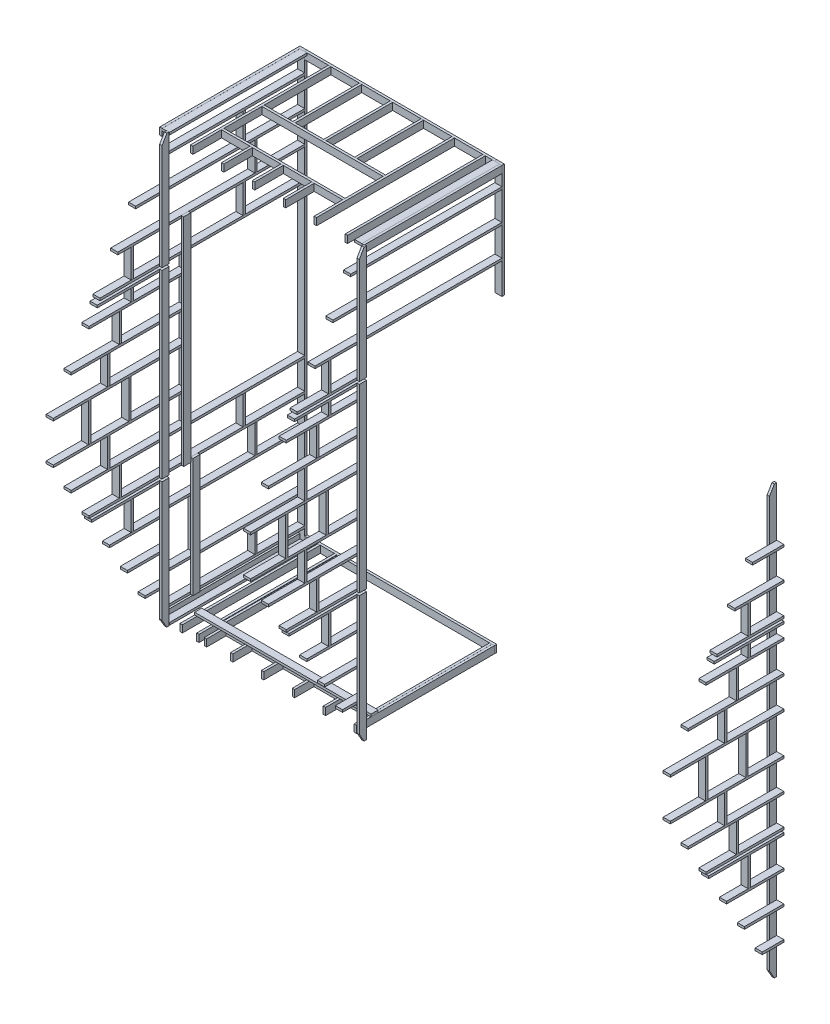
SolidWorks part; units mm, degrees
ref_plane "Спереди" through (0, 0, 0) normal (0, 0, 1) x (1, 0, 0)
ref_plane "Сверху" through (0, 0, 0) normal (0, 1, 0) x (1, 0, 0)
ref_plane "Справа" through (0, 0, 0) normal (1, 0, 0) x (0, 0, -1)
other "Configuration Table"
sketch "Эскиз2" plane through (-110, 0, 0) normal (-1, 0, 0) x (0, 0, 1)
  line L0 (-50, 0) -> (-50, 6600) construction
  line L1 (-50, 2700) -> (1529.9782, 2700)
  line L2 (-50, 2700) -> (-50, 2650)
  line L3 (-50, 2650) -> (1529.9782, 2650)
  line L4 (1529.9782, 2700) -> (1529.9782, 2650)
  line L5 (-50, 4100) -> (2338.2686, 4100)
  line L6 (-50, 4100) -> (-50, 4050)
  line L7 (-50, 4050) -> (2338.2686, 4050)
  line L8 (2338.2686, 4100) -> (2338.2686, 4050)
  line L9 (2651.9993, 4500) -> (-50, 4500) construction
  line L10 (-50, 8900) -> (-50, 100) construction
  line L11 (0, 0) -> (2598.0762, 4500) construction
  line L12 (2651.9993, 4500) -> (53.923, 0) construction
  line L13 (0, 9000) -> (2598.0762, 4500) construction
  line L14 (1550, 4100) -> (750, 4100) construction
  line L15 (-50, 4900) -> (-50, 4950)
  line L16 (-50, 4900) -> (2338.2686, 4900)
  line L17 (2338.2686, 4900) -> (2338.2686, 4950)
  line L18 (-50, 4950) -> (2338.2686, 4950)
  line L19 (1550, 4100) -> (1550, 4900) construction
  line L28 (1550, 4899) -> (1600, 4899)
  line L29 (1550, 4899) -> (1550, 4101)
  line L30 (1550, 4101) -> (1600, 4101)
  line L31 (1600, 4899) -> (1600, 4101)
  line L32 (750, 4100) -> (750, 4900) construction
  line L33 (750, 4899) -> (700, 4899)
  line L34 (750, 4899) -> (750, 4101)
  line L35 (750, 4101) -> (700, 4101)
  line L36 (700, 4899) -> (700, 4101)
  line L38 (1962.9909, 3400) -> (-50, 3400)
  line L39 (1962.9909, 3400) -> (1962.9909, 3450)
  line L40 (1962.9909, 3450) -> (-50, 3450)
  line L41 (-50, 3400) -> (-50, 3450)
  line L43 (-50, 2800) -> (1587.7132, 2800)
  line L44 (-50, 2800) -> (-50, 2750)
  line L45 (-50, 2750) -> (1587.7132, 2750)
  line L46 (1587.7132, 2800) -> (1587.7132, 2750)
  line L47 (1154.7005, 2000) -> (-50, 2000)
  line L48 (1154.7005, 2000) -> (1154.7005, 2050)
  line L49 (1154.7005, 2050) -> (-50, 2050)
  line L50 (-50, 2000) -> (-50, 2050)
  line L51 (779.4229, 1350) -> (-50, 1350)
  line L52 (779.4229, 1350) -> (779.4229, 1400)
  line L53 (779.4229, 1400) -> (-50, 1400)
  line L54 (-50, 1350) -> (-50, 1400)
  line L55 (404.1452, 700) -> (-50, 700)
  line L56 (404.1452, 700) -> (404.1452, 750)
  line L57 (404.1452, 750) -> (-50, 750)
  line L58 (-50, 700) -> (-50, 750)
  line L59 (1200, 4049) -> (1150, 4049)
  line L60 (1200, 4049) -> (1200, 3451)
  line L61 (1200, 3451) -> (1150, 3451)
  line L62 (1150, 4049) -> (1150, 3451)
  line L63 (950, 3399) -> (900, 3399)
  line L64 (950, 3399) -> (950, 2801)
  line L65 (950, 2801) -> (900, 2801)
  line L66 (900, 3399) -> (900, 2801)
  line L67 (700, 2649) -> (650, 2649)
  line L68 (700, 2649) -> (700, 2051)
  line L69 (700, 2051) -> (650, 2051)
  line L70 (650, 2649) -> (650, 2051)
  line L71 (1200, 4951) -> (1150, 4951)
  line L80 (900, 5601) -> (900, 6199)
  line L81 (950, 6199) -> (900, 6199)
  line L82 (950, 5601) -> (950, 6199)
  line L83 (950, 5601) -> (900, 5601)
  line L84 (1150, 4951) -> (1150, 5549)
  line L85 (1200, 5549) -> (1150, 5549)
  line L86 (1200, 4951) -> (1200, 5549)
  line L95 (1587.7132, 6200) -> (1587.7132, 6250)
  line L96 (-50, 6250) -> (1587.7132, 6250)
  line L97 (-50, 6200) -> (-50, 6250)
  line L98 (-50, 6200) -> (1587.7132, 6200)
  line L99 (-50, 5600) -> (-50, 5550)
  line L100 (1962.9909, 5550) -> (-50, 5550)
  line L101 (1962.9909, 5600) -> (1962.9909, 5550)
  line L102 (1962.9909, 5600) -> (-50, 5600)
  line L107 (-50, 4500) -> (-50, 9000) construction
  line L108 (-50, 9000) -> (0, 9000) construction
  line L110 (-50, 6550) -> (1414.5082, 6550)
  line L111 (-50, 6550) -> (-50, 6500)
  line L112 (-50, 6500) -> (1414.5082, 6500)
  line L113 (1414.5082, 6550) -> (1414.5082, 6500)
  line L114 (-50, 6600) -> (1356.7731, 6600)
  line L115 (-50, 6600) -> (-50, 6650)
  line L116 (-50, 6650) -> (1356.7731, 6650)
  line L117 (1356.7731, 6600) -> (1356.7731, 6650)
  line L118 (-50, 7300) -> (981.4955, 7300)
  line L119 (-50, 7300) -> (-50, 7250)
  line L120 (-50, 7250) -> (981.4955, 7250)
  line L121 (981.4955, 7300) -> (981.4955, 7250)
  line L122 (650, 6499) -> (700, 6499)
  line L123 (650, 6499) -> (650, 6251)
  line L124 (650, 6251) -> (700, 6251)
  line L125 (700, 6499) -> (700, 6251)
  line L126 (650, 7249) -> (700, 7249)
  line L127 (650, 7249) -> (650, 6651)
  line L128 (650, 6651) -> (700, 6651)
  line L129 (700, 7249) -> (700, 6651)
  line L130 (-50, 7950) -> (606.2178, 7950)
  line L131 (-50, 7950) -> (-50, 7900)
  line L132 (-50, 7900) -> (606.2178, 7900)
  line L133 (606.2178, 7950) -> (606.2178, 7900)
  dimension "D1" = 50
  dimension "D2" = 800
  dimension "D3" = 1
  dimension "D4" = 1
  dimension "D5" = 600
  dimension "D6" = 600
  dimension "D7" = 600
  dimension "D8" = 600
  dimension "D9" = 600
  dimension "D10" = 1
  dimension "D11" = 1
  dimension "D12" = 400
  dimension "D13" = 1
  dimension "D14" = 1
  dimension "D15" = 200
  dimension "D16" = 200
  dimension "D17" = 1
  dimension "D18" = 1
  dimension "D19" = 200
  dimension "D20" = 600
  dimension "D21" = 1
  dimension "D22" = 1
  dimension "D23" = 600
ref_plane "Плоскость1" through (-8990, 0, 0) normal (1, 0, 0) x (0, 0, -1)
ref_plane "Плоскость2" through (-13140, 0, 0) normal (1, 0, 0) x (0, 0, -1)
extrude "Бобышка-Вытянуть1" add sketch "Эскиз2" along normal blind 50 and the other way blind 100
extrude "Бобышка-Вытянуть2" add sketch "Эскиз2<2>" against normal blind 150 from surface separate body starting at plane "Плоскость1"
sketch "Эскиз2<2>" plane through (-110, 0, 0) normal (-1, 0, 0) x (0, 0, 1) same geometry as "Эскиз2"
extrude "Бобышка-Вытянуть3" add sketch "Эскиз2<3>" against normal blind 150 from surface separate body starting at plane "Плоскость2"
sketch "Эскиз2<3>" plane through (-110, 0, 0) normal (-1, 0, 0) x (0, 0, 1) same geometry as "Эскиз2"
sketch "Эскиз3" plane through (-160, 0, 0) normal (-1, 0, 0) x (0, 0, 1)
  line L0 (0, 0) -> (100, 173.2051)
  line L1 (-50, 2700) -> (100, 2700)
  line L2 (-50, 2700) -> (-50, 0)
  line L3 (-50, 0) -> (0, 0)
  line L4 (100, 2700) -> (100, 173.2051)
  line L5 (0, 0) -> (2598.0762, 4500) construction
  line L7 (-50, 2750) -> (100, 2750)
  line L8 (-50, 2750) -> (-50, 6550)
  line L9 (-50, 6550) -> (100, 6550)
  line L10 (100, 2750) -> (100, 6550)
  line L11 (-50, 6600) -> (1356.7731, 6600) construction
  line L12 (2598.0762, 4500) -> (-50, 4500) construction
  line L13 (-50, 6600) -> (100, 6600)
  line L14 (100, 6600) -> (100, 8826.7949)
  line L15 (0, 9000) -> (100, 8826.7949)
  line L16 (-50, 9000) -> (0, 9000)
  line L17 (-50, 6600) -> (-50, 9000)
  line L18 (1414.5082, 6550) -> (-50, 6550) construction
  dimension "D1" = 150
extrude "Бобышка-Вытянуть4" add sketch "Эскиз3" along normal blind 50 separate body
extrude "Бобышка-Вытянуть5" add sketch "Эскиз3<2>" against normal blind 50 from surface separate body starting at face at (-8840, 6950, 675)
sketch "Эскиз3<2>" plane through (-160, 0, 0) normal (-1, 0, 0) x (0, 0, 1) same geometry as "Эскиз3"
extrude "Бобышка-Вытянуть6" add sketch "Эскиз3<3>" against normal blind 50 from surface separate body starting at face at (-12990, 7275, 465.7477)
sketch "Эскиз3<3>" plane through (-160, 0, 0) normal (-1, 0, 0) x (0, 0, 1) same geometry as "Эскиз3"
ref_plane "Плоскость3" through (0, 0, -3000) normal (0, 0, -1) x (-1, 0, 0)
sketch "Эскиз4" plane through (0, 0, -3000) normal (0, 0, -1) x (-1, 0, 0)
  line L1 (8840, 8990) -> (8990, 8990)
  line L2 (8840, 8990) -> (8840, 6600)
  line L3 (8840, 6600) -> (8990, 6600)
  line L4 (8990, 8990) -> (8990, 6600)
  line L5 (12990, 8990) -> (13140, 8990)
  line L6 (12990, 8990) -> (12990, 10)
  line L7 (12990, 10) -> (13140, 10)
  line L8 (13140, 8990) -> (13140, 10)
  line L9 (8991, 8990) -> (12989, 8990)
  line L10 (8991, 8990) -> (8991, 8840)
  line L11 (8991, 8840) -> (12989, 8840)
  line L12 (12989, 8990) -> (12989, 8840)
  line L13 (9000, 160) -> (12989, 160)
  line L14 (9000, 160) -> (9000, 10)
  line L15 (9000, 10) -> (12989, 10)
  line L16 (12989, 160) -> (12989, 10)
  line L17 (8990, 7950) -> (8990, 7900) construction
  line L18 (12990, 6600) -> (12990, 9000) construction
  line L20 (12940, 0) -> (12990, 0) construction
  line L21 (8840, 6600) -> (8840, 9000) construction
  line L22 (8790, 9000) -> (8840, 9000) construction
  line L23 (8840, 6600) -> (8990, 6600) construction
  line L24 (8990, 6650) -> (8990, 6600) construction
  line L26 (9000, 203) -> (9000, 1000) construction
  point P26 (9000, 85)
  dimension "D1" = 1
  dimension "D2" = 150
  dimension "D3" = 1
  dimension "D4" = 1
  dimension "D5" = 10
  dimension "D6" = 10
extrude "Бобышка-Вытянуть7" add sketch "Эскиз4" against normal blind 50 separate body
sketch "Эскиз5" plane through (-8990, 0, 0) normal (-1, 0, 0) x (0, 0, 1)
  line L0 (-2950, 6600) -> (-2950, 8990) construction
  line L1 (-50, 7300) -> (-2950, 7300)
  line L2 (-50, 7300) -> (-50, 7250)
  line L3 (-50, 7250) -> (-2950, 7250)
  line L4 (-2950, 7300) -> (-2950, 7250)
  line L5 (-50, 7900) -> (606.2178, 7900) construction
  line L6 (-50, 7950) -> (-2950, 7950)
  line L7 (-50, 7950) -> (-50, 7900)
  line L8 (-50, 7900) -> (-2950, 7900)
  line L9 (-2950, 7950) -> (-2950, 7900)
  line L10 (230.9401, 8600) -> (-2950, 8600)
  line L11 (230.9401, 8600) -> (230.9401, 8550)
  line L12 (230.9401, 8550) -> (-2950, 8550)
  line L13 (-2950, 8600) -> (-2950, 8550)
  line L14 (0, 9000) -> (2598.0762, 4500) construction
  dimension "D1" = 600
extrude "Бобышка-Вытянуть8" add sketch "Эскиз5" against normal up to vertex (150 mm away) separate body up to point (-8840, 7950, -50)
sketch "Эскиз6" plane through (-8840, 0, 0) normal (-1, 0, 0) x (0, 0, 1)
  line L1 (-2950, 8990) -> (-50, 8990)
  line L2 (-2950, 8990) -> (-2950, 8840)
  line L3 (-2950, 8840) -> (-50, 8840)
  line L4 (-50, 8990) -> (-50, 8840)
  line L5 (-50, 6600) -> (-50, 9000) construction
  point P5 (0, 0)
  point P6 (-50, 8990)
  dimension "D1" = 150
extrude "Бобышка-Вытянуть9" add sketch "Эскиз6" along normal blind 50 separate body
sketch "Эскиз7" plane through (0, 0, -2950) normal (0, 0, 1) x (1, 0, 0)
  line L0 (-8991, 8840) -> (-12989, 8840) construction
  line L1 (-13140, 8990) -> (-13090, 8990)
  line L2 (-13140, 8990) -> (-13140, 8840)
  line L3 (-13140, 8840) -> (-13090, 8840)
  line L4 (-13090, 8990) -> (-13090, 8840)
  line L5 (-8890, 8990) -> (-8840, 8990) construction
  line L6 (-13140, 8990) -> (-12990, 8990) construction
  line L7 (-13089, 8990) -> (-12939, 8990)
  line L8 (-13089, 8990) -> (-13089, 8940)
  line L9 (-13089, 8940) -> (-12939, 8940)
  line L10 (-12939, 8990) -> (-12939, 8940)
  line L11 (-12989, 8990) -> (-8991, 8990) construction
  line L12 (-9040, 8990) -> (-8890, 8990)
  line L13 (-9040, 8990) -> (-9040, 8940)
  line L14 (-9040, 8940) -> (-8890, 8940)
  line L15 (-8890, 8990) -> (-8890, 8940)
  line L16 (-8890, 8840) -> (-8890, 8990) construction
  line L17 (-8890, 8840) -> (-8840, 8840) construction
  line L19 (-12490, 8990) -> (-12440, 8990)
  line L20 (-12490, 8990) -> (-12490, 8840)
  line L21 (-12490, 8840) -> (-12440, 8840)
  line L22 (-12440, 8990) -> (-12440, 8840)
  line L23 (-11840, 8990) -> (-11790, 8990)
  line L24 (-11840, 8990) -> (-11840, 8840)
  line L25 (-11840, 8840) -> (-11790, 8840)
  line L26 (-11790, 8990) -> (-11790, 8840)
  line L27 (-11190, 8990) -> (-11140, 8990)
  line L28 (-11190, 8990) -> (-11190, 8840)
  line L29 (-11190, 8840) -> (-11140, 8840)
  line L30 (-11140, 8990) -> (-11140, 8840)
  line L31 (-10540, 8990) -> (-10490, 8990)
  line L32 (-10540, 8990) -> (-10540, 8840)
  line L33 (-10540, 8840) -> (-10490, 8840)
  line L34 (-10490, 8990) -> (-10490, 8840)
  line L35 (-9890, 8990) -> (-9840, 8990)
  line L36 (-9890, 8990) -> (-9890, 8840)
  line L37 (-9890, 8840) -> (-9840, 8840)
  line L38 (-9840, 8990) -> (-9840, 8840)
  line L39 (-9240, 8990) -> (-9190, 8990)
  line L40 (-9240, 8990) -> (-9240, 8840)
  line L41 (-9240, 8840) -> (-9190, 8840)
  line L42 (-9190, 8990) -> (-9190, 8840)
  dimension "D1" = 1
  dimension "D2" = 600
  dimension "D3" = 600
  dimension "D4" = 600
  dimension "D5" = 600
  dimension "D6" = 600
  dimension "D7" = 600
  dimension "D8" = 300
extrude "Бобышка-Вытянуть10" add sketch "Эскиз7" along normal up to surface (2900 mm away) separate body up to face at (-8865, 8915, -50)
sketch "Эскиз8" plane through (0, 9000, 0) normal (0, 1, 0) x (1, 0, 0)
  line L2 (-9890, 650) -> (-12440, 650)
  line L3 (-9890, 650) -> (-9890, 1550)
  line L4 (-9890, 1550) -> (-12440, 1550)
  line L5 (-12440, 650) -> (-12440, 1550)
  line L7 (-9890, 700) -> (-12440, 700) construction
  line L8 (-12440, 1500) -> (-9890, 1500) construction
  line L9 (-12440, 50) -> (-12440, 2950) construction
  line L10 (-9890, 50) -> (-9890, 2950) construction
  dimension "D1" = 50
  dimension "D2" = 50
extrude "Вырез-Вытянуть1" cut sketch "Эскиз8" against normal blind 488
sketch "Эскиз9" plane through (0, 8840, 0) normal (0, -1, 0) x (1, 0, 0)
  line L0 (-12440, -50) -> (-12440, -2950) construction
  line L1 (-12440, -650) -> (-9890, -650)
  line L2 (-12440, -650) -> (-12440, -700)
  line L3 (-12440, -700) -> (-9890, -700)
  line L4 (-9890, -650) -> (-9890, -700)
  line L7 (-12440, -1500) -> (-9890, -1500)
  line L8 (-12440, -1500) -> (-12440, -1550)
  line L9 (-12440, -1550) -> (-9890, -1550)
  line L10 (-9890, -1500) -> (-9890, -1550)
  line L11 (-11840, -650) -> (-11790, -650) construction
  line L12 (-9890, -50) -> (-9890, -2950) construction
  line L13 (-11140, -1550) -> (-11190, -1550) construction
  line L14 (-9840, -50) -> (-9890, -50) construction
extrude "Бобышка-Вытянуть11" add sketch "Эскиз9" against normal up to surface (150 mm away) separate body up to face at (-8915, 8990, -2975)
combine bodies "Соединить1" operation type add bodies to combine 142 185
combine bodies "Соединить2" operation type add bodies to combine 179 186
sketch "Эскиз10" plane through (-12990, 0, 0) normal (1, 0, 0) x (0, 0, -1)
  line L0 (505.6624, 3450) -> (505.6624, 6600) construction
  line L1 (50, 6600) -> (2950, 6600)
  line L2 (50, 6600) -> (50, 6650)
  line L3 (50, 6650) -> (2950, 6650)
  line L4 (2950, 6600) -> (2950, 6650)
  line L5 (50, 7250) -> (2950, 7250)
  line L6 (50, 7250) -> (50, 7300)
  line L7 (50, 7300) -> (2950, 7300)
  line L8 (2950, 7250) -> (2950, 7300)
  line L9 (50, 7900) -> (2950, 7900)
  line L10 (50, 7900) -> (50, 7950)
  line L11 (50, 7950) -> (2950, 7950)
  line L12 (2950, 7900) -> (2950, 7950)
  line L13 (50, 6200) -> (454.6624, 6200)
  line L14 (50, 6200) -> (50, 6250)
  line L15 (50, 6250) -> (454.6624, 6250)
  line L17 (50, 5550) -> (454.6624, 5550)
  line L18 (50, 5550) -> (50, 5600)
  line L19 (50, 5600) -> (454.6624, 5600)
  line L20 (454.6624, 5550) -> (454.6624, 5600)
  line L21 (50, 4900) -> (454.6624, 4900)
  line L22 (50, 4900) -> (50, 4950)
  line L23 (50, 4950) -> (454.6624, 4950)
  line L24 (454.6624, 4900) -> (454.6624, 4950)
  line L25 (50, 4050) -> (454.6624, 4050)
  line L26 (50, 4050) -> (50, 4100)
  line L27 (50, 4100) -> (454.6624, 4100)
  line L28 (454.6624, 4050) -> (454.6624, 4100)
  line L29 (50, 3400) -> (2950, 3400)
  line L30 (50, 3400) -> (50, 3450)
  line L31 (50, 3450) -> (2950, 3450)
  line L32 (2950, 3400) -> (2950, 3450)
  line L33 (455.6624, 6599) -> (505.6624, 6599)
  line L34 (455.6624, 6599) -> (455.6624, 3451)
  line L35 (455.6624, 3451) -> (505.6624, 3451)
  line L36 (505.6624, 6599) -> (505.6624, 3451)
  line L37 (2950, 8990) -> (2950, 10) construction
  line L38 (50, 6600) -> (50, 9000) construction
  line L39 (-650, 6651) -> (-700, 6651) construction
  line L40 (-50, 6600) -> (-1166.3586, 6600) construction
  line L41 (50, 7250) -> (-981.4955, 7250) construction
  line L42 (50, 7900) -> (-606.2178, 7900) construction
  line L43 (50, 4050) -> (-2338.2686, 4050) construction
  line L44 (50, 4900) -> (-2338.2686, 4900) construction
  line L45 (50, 5550) -> (-1962.9909, 5550) construction
  line L46 (50, 6200) -> (-1587.7132, 6200) construction
  line L47 (-1962.9909, 3450) -> (50, 3450) construction
  line L48 (50, 0) -> (50, 2700) construction
  line L49 (50, 8550) -> (2950, 8550)
  line L50 (50, 8550) -> (50, 8600)
  line L51 (50, 8600) -> (2950, 8600)
  line L52 (2950, 8550) -> (2950, 8600)
  line L53 (50, 2750) -> (2950, 2750)
  line L54 (50, 2750) -> (50, 2800)
  line L55 (50, 2800) -> (2950, 2800)
  line L56 (2950, 2750) -> (2950, 2800)
  line L57 (50, 2100) -> (2950, 2100)
  line L58 (50, 2100) -> (50, 2150)
  line L59 (50, 2150) -> (2950, 2150)
  line L60 (2950, 2100) -> (2950, 2150)
  line L61 (-650, 2051) -> (-700, 2051) construction
  line L62 (700, 2100) -> (3000, 2100) construction
  line L63 (454.6624, 6250) -> (454.6624, 6200)
  line L68 (50, 2750) -> (50, 6550) construction
  line L73 (3000, 1000) -> (700, 1000) construction
  line L74 (50, 1000) -> (2950, 1000)
  line L75 (50, 1000) -> (50, 950)
  line L76 (50, 950) -> (2950, 950)
  line L77 (2950, 1000) -> (2950, 950)
  line L78 (700, 1000) -> (700, 2100) construction
  line L79 (700, 1001) -> (650, 1001)
  line L80 (700, 1001) -> (700, 2099)
  line L81 (700, 2099) -> (650, 2099)
  line L82 (650, 1001) -> (650, 2099)
  line L84 (50, 350) -> (2950, 350)
  line L85 (50, 350) -> (50, 300)
  line L86 (50, 300) -> (2950, 300)
  line L87 (2950, 350) -> (2950, 300)
  line L88 (1650, 3399) -> (1700, 3399)
  line L89 (1650, 3399) -> (1650, 2801)
  line L90 (1650, 2801) -> (1700, 2801)
  line L91 (1700, 3399) -> (1700, 2801)
  line L92 (1900, 2749) -> (1950, 2749)
  line L93 (1900, 2749) -> (1900, 2151)
  line L94 (1900, 2151) -> (1950, 2151)
  line L95 (1950, 2749) -> (1950, 2151)
  line L96 (1900, 949) -> (1950, 949)
  line L97 (1900, 949) -> (1900, 351)
  line L98 (1900, 351) -> (1950, 351)
  line L99 (1950, 949) -> (1950, 351)
  line L100 (1650, 8549) -> (1700, 8549)
  line L101 (1650, 8549) -> (1650, 7951)
  line L102 (1650, 7951) -> (1700, 7951)
  line L103 (1700, 8549) -> (1700, 7951)
  line L104 (1900, 7899) -> (1950, 7899)
  line L105 (1900, 7899) -> (1900, 7301)
  line L106 (1900, 7301) -> (1950, 7301)
  line L107 (1950, 7899) -> (1950, 7301)
  line L108 (1650, 7249) -> (1700, 7249)
  line L109 (1650, 7249) -> (1650, 6651)
  line L110 (1650, 6651) -> (1700, 6651)
  line L111 (1700, 7249) -> (1700, 6651)
  dimension "D1" = 1
  dimension "D2" = 1
  dimension "D3" = 1
  dimension "D4" = 600
  dimension "D5" = 1100
  dimension "D6" = 1
  dimension "D7" = 1
  dimension "D8" = 600
  dimension "D9" = 1000
  dimension "D10" = 200
  dimension "D11" = 1
  dimension "D12" = 1
  dimension "D13" = 1
  dimension "D14" = 1
  dimension "D15" = 1
  dimension "D16" = 1
  dimension "D17" = 1
extrude "Бобышка-Вытянуть12" add sketch "Эскиз10" against normal up to surface (150 mm away) separate body up to face at (-13140, 2025, 552.3503)
sketch "Эскиз11" plane through (-12990, 0, 0) normal (1, 0, 0) x (0, 0, -1)
  line L0 (50, 2750) -> (2950, 2750) construction
  line L1 (355.6624, 2750) -> (505.6624, 2750)
  line L2 (355.6624, 2750) -> (355.6624, 7300)
  line L3 (355.6624, 7300) -> (505.6624, 7300)
  line L4 (505.6624, 2750) -> (505.6624, 7300)
  line L5 (2950, 7300) -> (50, 7300) construction
  line L6 (-100, 2750) -> (50, 2750) construction
  line L7 (505.6624, 3451) -> (505.6624, 6599) construction
  line L8 (50, 300) -> (2950, 300) construction
  line L9 (550, 300) -> (700, 300)
  line L10 (550, 300) -> (550, 2800)
  line L11 (550, 2800) -> (700, 2800)
  line L12 (700, 300) -> (700, 2800)
  line L13 (2950, 2800) -> (50, 2800) construction
  line L14 (700, 1001) -> (700, 2099) construction
extrude "Бобышка-Вытянуть13" add sketch "Эскиз11" along normal blind 50 separate body
sketch "Эскиз12" plane through (0, 0, -2950) normal (0, 0, 1) x (1, 0, 0)
  line L1 (-9000, 10) -> (-12989, 10) construction
  line L2 (-13140, 10) -> (-13090, 10)
  line L3 (-13140, 10) -> (-13140, 160)
  line L4 (-13140, 160) -> (-13090, 160)
  line L5 (-13090, 10) -> (-13090, 160)
  line L6 (-12939, 10) -> (-13089, 10)
  line L7 (-12939, 10) -> (-12939, 60)
  line L8 (-12939, 60) -> (-13089, 60)
  line L9 (-13089, 10) -> (-13089, 60)
  line L10 (-12989, 10) -> (-12989, 160) construction
  line L12 (-12990, 300) -> (-12990, 350) construction
  dimension "D1" = 1
extrude "Бобышка-Вытянуть14" add sketch "Эскиз12" along normal up to surface (2900 mm away) separate body
sketch "Эскиз13" plane through (0, 10, 0) normal (0, 1, 0) x (1, 0, 0)
  line L0 (-12989, 2950) -> (-9000, 2950) construction
  line L1 (-9000, 2950) -> (-9050, 2950)
  line L2 (-9000, 2950) -> (-9000, 50)
  line L3 (-9000, 50) -> (-9050, 50)
  line L4 (-9050, 2950) -> (-9050, 50)
  line L8 (-9051, 2950) -> (-9100, 2950)
  line L9 (-9051, 2950) -> (-9051, 506.6624)
  line L10 (-9051, 506.6624) -> (-9100, 506.6624)
  line L11 (-9100, 2950) -> (-9100, 506.6624)
  line L12 (-9100, 505.6624) -> (-12250, 505.6624) construction
  line L17 (-9051, 505.6624) -> (-12300, 505.6624)
  line L18 (-9051, 505.6624) -> (-9051, 455.6624)
  line L19 (-9051, 455.6624) -> (-12300, 455.6624)
  line L20 (-12300, 505.6624) -> (-12300, 455.6624)
  line L24 (-12300, 2950) -> (-12250, 2950)
  line L25 (-12300, 2950) -> (-12300, 506.6624)
  line L26 (-12300, 506.6624) -> (-12250, 506.6624)
  line L27 (-12250, 2950) -> (-12250, 506.6624)
  line L28 (470, 50) -> (-13620, 50) construction
  line L29 (-12312, 2950) -> (-12362, 2950)
  line L30 (-12312, 2950) -> (-12312, 49)
  line L31 (-12312, 49) -> (-12362, 49)
  line L32 (-12362, 2950) -> (-12362, 49)
  line L33 (-12662, 2950) -> (-12712, 2950)
  line L34 (-12662, 2950) -> (-12662, 50)
  line L35 (-12662, 50) -> (-12712, 50)
  line L36 (-12712, 2950) -> (-12712, 50)
  line L37 (470, 49) -> (-13620, 49) construction
  line L38 (-12312, 49) -> (-9050, 50) construction
  line L39 (-12312, 454.6624) -> (-9050, 454.6624) construction
  line L40 (-13000, 50) -> (-9000, 50) construction
  line L41 (-12200, 454.6624) -> (-12150, 454.6624)
  line L42 (-12200, 454.6624) -> (-12200, 49.0497)
  line L43 (-12200, 49.0497) -> (-12150, 49.0497)
  line L44 (-12150, 454.6624) -> (-12150, 49.0497)
  line L45 (-11650, 454.6624) -> (-11600, 454.6624)
  line L46 (-11650, 454.6624) -> (-11650, 49.2183)
  line L47 (-11650, 49.2183) -> (-11600, 49.2183)
  line L48 (-11600, 454.6624) -> (-11600, 49.2183)
  line L49 (-11000, 454.6624) -> (-10950, 454.6624)
  line L50 (-11000, 454.6624) -> (-11000, 50)
  line L51 (-11000, 50) -> (-10950, 50)
  line L52 (-10950, 454.6624) -> (-10950, 50)
  line L53 (-10350, 454.6624) -> (-10300, 454.6624)
  line L54 (-10350, 454.6624) -> (-10350, 49.6168)
  line L55 (-10350, 49.6168) -> (-10300, 49.6168)
  line L56 (-10300, 454.6624) -> (-10300, 49.6168)
  line L57 (-9700, 454.6624) -> (-9650, 454.6624)
  line L58 (-9700, 454.6624) -> (-9700, 49.8161)
  line L59 (-9700, 49.8161) -> (-9650, 49.8161)
  line L60 (-9650, 454.6624) -> (-9650, 49.8161)
  point P55 (-10930.7512, 50)
  dimension "D1" = 50
  dimension "D2" = 49
  dimension "D3" = 1
  dimension "D4" = 1
  dimension "D5" = 50
  dimension "D6" = 1
  dimension "D7" = 3150
  dimension "D8" = 50
  dimension "D9" = 12
  dimension "D10" = 300
  dimension "D11" = 600
  dimension "D12" = 600
  dimension "D13" = 600
  dimension "D14" = 600
  dimension "D15" = 500
  dimension "D16" = 1
extrude "Бобышка-Вытянуть15" add sketch "Эскиз13" along normal blind 150 separate body
sketch "Эскиз14" plane through (0, 160, 0) normal (0, 1, 0) x (1, 0, 0)
  line L0 (-9000, 50) -> (-9000, 2950) construction
  line L1 (-9000, 505.6624) -> (-12712, 505.6624)
  line L2 (-9000, 505.6624) -> (-9000, 355.6624)
  line L3 (-9000, 355.6624) -> (-12712, 355.6624)
  line L4 (-12712, 505.6624) -> (-12712, 355.6624)
  line L5 (-12712, 2950) -> (-12712, 50) construction
  line L6 (-9051, 505.6624) -> (-12300, 505.6624) construction
  dimension "D1" = 150
extrude "Бобышка-Вытянуть16" add sketch "Эскиз14" along normal blind 50 separate body
